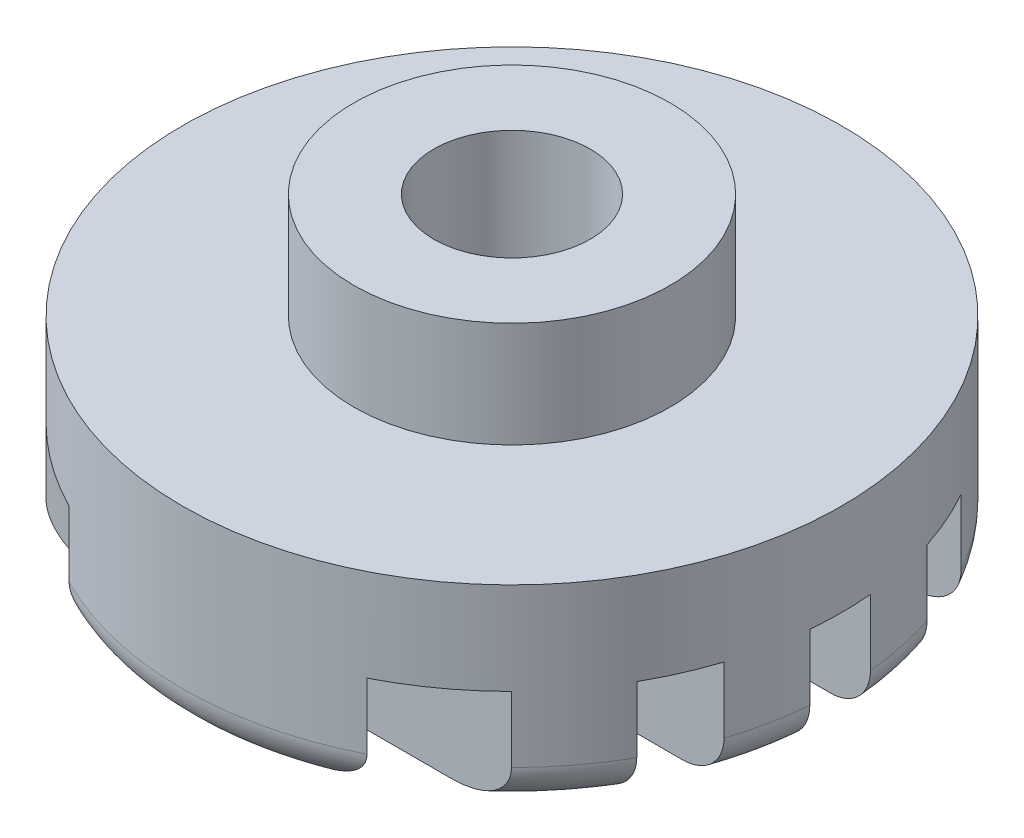
SolidWorks part; units mm, degrees
ref_plane "Front Plane" through (0, 0, 0) normal (0, 0, 1) x (1, 0, 0)
ref_plane "Top Plane" through (0, 0, 0) normal (0, 1, 0) x (1, 0, 0)
ref_plane "Right Plane" through (0, 0, 0) normal (1, 0, 0) x (0, 0, -1)
sketch "Sketch1" plane through (0, 0, 0) normal (0, 1, 0) x (1, 0, 0)
  circle A0 centre (0, 0) radius 25
  dimension "D1" = 50
extrude "Boss-Extrude1" add sketch "Sketch1" along normal blind 15
sketch "Sketch14" plane through (0, 0, 0) normal (0, 1, 0) x (1, 0, 0)
  line L1 (-26.93, 2.2997) -> (26.93, 2.2997)
  line L2 (-26.93, 2.2997) -> (-26.93, -2.2997)
  line L3 (-26.93, -2.2997) -> (26.93, -2.2997)
  line L4 (26.93, 2.2997) -> (26.93, -2.2997)
  line L5 (-26.93, 2.2997) -> (26.93, -2.2997) construction
  line L6 (-26.93, -2.2997) -> (26.93, 2.2997) construction
  point P0 (0, 0)
extrude "Cut-Extrude13" cut sketch "Sketch14" along normal blind 8
pattern_linear "LPattern11" count 4 spacing 10 along (0, 0, 1) count 4 spacing 10 along (0, 0, -1) of "Cut-Extrude13"
sketch "Sketch16" plane through (0, 15, 0) normal (0, 1, 0) x (1, 0, 0)
  circle A0 centre (0, 0) radius 12
  circle A1 centre (0, 0) radius 12
  dimension "D1" = 24
sketch "Sketch18" plane through (0, 0, 0) normal (0, -1, 0) x (1, 0, 0)
  circle A0 centre (0, 0) radius 10.0316
extrude "Cut-Extrude15" cut sketch "Sketch18" against normal blind 8
extrude "Boss-Extrude3" add sketch "Sketch16" along normal blind 8 contours A0
sketch "Sketch19" plane through (0, 23, 0) normal (0, 1, 0) x (1, 0, 0)
  circle A0 centre (0, 0) radius 5.9349
extrude "Cut-Extrude16" cut sketch "Sketch19" against normal blind 26
fillet "Fillet2" radius 3 1 edges at (0, 0, 25)
fillet "Fillet3" radius 3 9 edges at (0, 0, -25) (19.8941, 0, -15.1401) (24.4886, 0, -5.0307) (24.4886, 0, 5.0307) (19.8941, 0, 15.1401) (-19.8941, 0, -15.1401) (-24.4886, 0, -5.0307) (-24.4886, 0, 5.0307) (-19.8941, 0, 15.1401)
